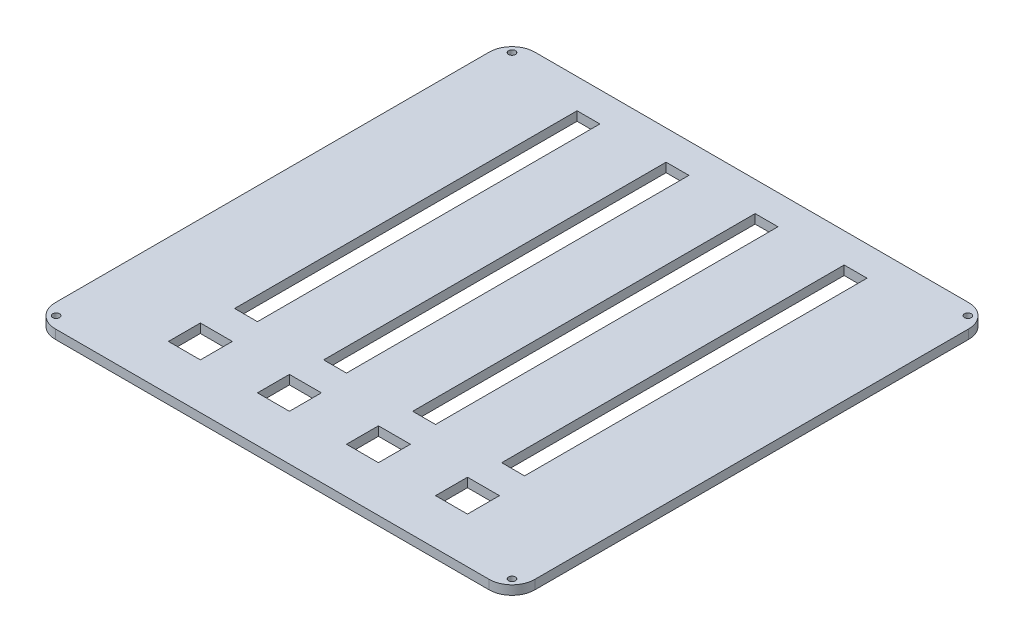
SolidWorks part; units mm, degrees
ref_plane "Front Plane" through (0, 0, 0) normal (0, 0, 1) x (1, 0, 0)
ref_plane "Top Plane" through (0, 0, 0) normal (0, 1, 0) x (1, 0, 0)
ref_plane "Right Plane" through (0, 0, 0) normal (1, 0, 0) x (0, 0, -1)
sketch "Sketch1" plane through (0, 0, 0) normal (0, 1, 0) x (1, 0, 0)
  line L0 (-101, -101) -> (-101, 101)
  line L5 (-105, -105) -> (105, -105)
  line L6 (-105, -105) -> (-105, 105)
  line L7 (-105, 105) -> (105, 105)
  line L8 (105, -105) -> (105, 105)
  line L9 (-101, 101) -> (101, 101)
  line L10 (101, -101) -> (101, 101)
  line L11 (-101, -101) -> (101, -101)
  line L12 (-101, 101) -> (-99.8333, 99.8333) construction
  line L13 (-55, 0) -> (55, 0) construction
  line L14 (-101, -101) -> (-99.8333, -99.8333) construction
  line L15 (0, -55) -> (0, 55) construction
  line L16 (101, -101) -> (99.8333, -99.8333) construction
  line L17 (101, 101) -> (99.8333, 99.8333) construction
  circle A1 centre (-99.8333, 99.8333) radius 1.5
  circle A2 centre (-99.8333, -99.8333) radius 1.5
  circle A3 centre (99.8333, -99.8333) radius 1.5
  circle A4 centre (99.8333, 99.8333) radius 1.5
  point P0 (0, 0)
  point P6 (-105, 0)
  point P7 (0, 105)
  dimension "D3" = 4
  dimension "D4" = 3
  dimension "D1" = 210
  dimension "D2" = 210
  dimension "D5" = 1.65
  dimension "D6" = 45
extrude "MainExtrude" add sketch "Sketch1" along normal blind 4 contours L6 L5 L8 L7
extrude "ScrewHoles" cut sketch "Sketch1<6>" along normal up to surface (4 mm away) contours A1 | A2 | A3 | A4 up to face at (0, 4, 0)
sketch "Sketch1<6>" plane through (0, 0, 0) normal (0, 1, 0) x (1, 0, 0) same geometry as "Sketch1"
fillet "RoundedCorners" radius 10 4 edges at (-105, 2, -105) (-105, 2, 105) (105, 2, -105) (105, 2, 105)
sketch "Sketch2" plane through (0, 0, 0) normal (0, -1, 0) x (1, 0, 0)
  line L0 (-17.92, 37.135) -> (17.92, 37.135) construction
  line L1 (2.2, 0) -> (-2.2, 0) construction
  circle A0 centre (-17.92, 37.135) radius 0.98
  circle A1 centre (-17.92, 37.135) radius 2
  circle A2 centre (17.92, 37.135) radius 2
  circle A3 centre (17.92, 37.135) radius 0.98
  circle A4 centre (-17.92, -37.135) radius 0.98
  circle A5 centre (-17.92, -37.135) radius 2
  circle A6 centre (17.92, -37.135) radius 0.98
  circle A7 centre (17.92, -37.135) radius 2
  point P3 (0, 37.135)
  dimension "D1" = 1.96
  dimension "D2" = 4
  dimension "D4" = 37.135
  dimension "D5" = 35.84
  dimension "D6" = 74.27
  dimension "D3" = 2
extrude "PCBHoles" [suppressed] add sketch "Sketch2" along normal blind 2
fillet "PCBRounds" [suppressed] radius 2
sketch "Sketch3" plane through (0, 4, 0) normal (0, 1, 0) x (1, 0, 0)
  line L0 (-105, -95) -> (-105, 95) construction
  line L1 (-65.5, -85) -> (-51.5, -85)
  line L2 (-65.5, -85) -> (-65.5, -71)
  line L3 (-65.5, -71) -> (-51.5, -71)
  line L4 (-51.5, -85) -> (-51.5, -71)
  line L5 (-65.5, -85) -> (-51.5, -71) construction
  line L6 (-65.5, -71) -> (-51.5, -85) construction
  line L7 (-95, -105) -> (95, -105) construction
  line L8 (-26.5, -85) -> (-26.5, -71)
  line L9 (-26.5, -85) -> (-12.5, -85)
  line L10 (-12.5, -85) -> (-12.5, -71)
  line L11 (-26.5, -71) -> (-12.5, -71)
  line L12 (12.5, -85) -> (12.5, -71)
  line L13 (12.5, -85) -> (26.5, -85)
  line L14 (26.5, -85) -> (26.5, -71)
  line L15 (12.5, -71) -> (26.5, -71)
  line L16 (51.5, -85) -> (51.5, -71)
  line L17 (51.5, -85) -> (65.5, -85)
  line L18 (65.5, -85) -> (65.5, -71)
  line L19 (51.5, -71) -> (65.5, -71)
  line L20 (105, -95) -> (105, 95) construction
  line L21 (-24.5, 92) -> (-24.5, -58)
  line L22 (-63.5, 92) -> (-53.5, 92)
  line L23 (-63.5, 92) -> (-63.5, -58)
  line L24 (-63.5, -58) -> (-53.5, -58)
  line L25 (-53.5, 92) -> (-53.5, -58)
  line L26 (-63.5, 92) -> (-53.5, -58) construction
  line L27 (-63.5, -58) -> (-53.5, 92) construction
  line L28 (-24.5, 92) -> (-14.5, 92)
  line L29 (-14.5, 92) -> (-14.5, -58)
  line L30 (-24.5, -58) -> (-14.5, -58)
  line L31 (-24.5, -58) -> (-14.5, 92) construction
  line L32 (-24.5, 92) -> (-14.5, -58) construction
  line L33 (14.5, 92) -> (14.5, -58)
  line L34 (14.5, 92) -> (24.5, 92)
  line L35 (24.5, 92) -> (24.5, -58)
  line L36 (14.5, -58) -> (24.5, -58)
  line L37 (14.5, -58) -> (24.5, 92) construction
  line L38 (14.5, 92) -> (24.5, -58) construction
  line L39 (53.5, 92) -> (53.5, -58)
  line L40 (53.5, 92) -> (63.5, 92)
  line L41 (63.5, 92) -> (63.5, -58)
  line L42 (53.5, -58) -> (63.5, -58)
  line L43 (53.5, -58) -> (63.5, 92) construction
  line L44 (53.5, 92) -> (63.5, -58) construction
  line L45 (-26.5, -71) -> (-12.5, -85)
  line L46 (12.5, -71) -> (26.5, -85)
  line L47 (51.5, -71) -> (65.5, -85)
  line L49 (-70, 98) -> (70, 98) construction
  line L50 (-70, 98) -> (-70, -62) construction
  line L51 (-70, -62) -> (70, -62) construction
  line L52 (70, 98) -> (70, -62) construction
  line L53 (-70, 98) -> (70, -62) construction
  line L54 (-70, -62) -> (70, 98) construction
  point P0 (-58.5, -78)
  point P23 (-58.5, 17)
  point P29 (-19.5, 17)
  point P35 (19.5, 17)
  point P40 (58.5, 17)
  point P45 (-19.5, -78)
  point P46 (19.5, -78)
  point P47 (58.5, -78)
  dimension "D1" = 14
  dimension "D2" = 39.5
  dimension "D3" = 20
  dimension "D5" = 39.5
  dimension "D6" = 150
  dimension "D7" = 10
  dimension "D8" = 95
  dimension "D9" = 4
  dimension "D10" = 160
  dimension "D11" = 140
  dimension "D12" = 6.5
  dimension "D13" = 4
  dimension "D4" = 4
extrude "Cutouts" cut sketch "Sketch3" against normal blind 10 contours L23 L22 L25 L24 | L21 L30 L29 L28 | L33 L36 L35 L34 | L39 L42 L41 L40 | L2 L1 L4 L3 | L8 L11 L10 L9 | L12 L15 L14 L13 | L16 L19 L18 L17
sketch "Sketch4" plane through (0, 0, 0) normal (0, -1, 0) x (1, 0, 0)
  circle A0 centre (-70, 62) radius 1.25
  circle A1 centre (70, 62) radius 1.25
  circle A2 centre (70, -98) radius 1.25
  circle A3 centre (-70, -98) radius 1.25
  dimension "D1" = 2.5
sketch "Sketch5" plane through (0, 4, 0) normal (0, 1, 0) x (1, 0, 0)
  line L1 (-102.1071, -17.908) -> (-66.2671, -17.908) construction
  line L2 (-102.1071, -17.908) -> (-102.1071, -92.178) construction
  line L3 (-102.1071, -92.178) -> (-66.2671, -92.178) construction
  line L4 (-66.2671, -17.908) -> (-66.2671, -92.178) construction
  circle A0 centre (-102.1071, -17.908) radius 2
  circle A1 centre (-102.1071, -17.908) radius 0.98
  circle A2 centre (-66.2671, -17.908) radius 2
  circle A3 centre (-66.2671, -17.908) radius 0.98
  circle A4 centre (-66.2671, -92.178) radius 2
  circle A5 centre (-66.2671, -92.178) radius 0.98
  circle A6 centre (-102.1071, -92.178) radius 2
  circle A7 centre (-102.1071, -92.178) radius 0.98
  dimension "D3" = 4
  dimension "D4" = 1.96
  dimension "D1" = 35.84
  dimension "D2" = 74.27
extrude "Boss-Extrude1" [suppressed] add sketch "Sketch5" against normal blind 8
fillet "Fillet1" [suppressed] radius 0.5
sketch "Sketch6" plane through (0, 0, 0) normal (0, -1, 0) x (1, 0, 0)
  circle A0 centre (-70, 62) radius 2
  circle A1 centre (-70, 62) radius 0.98
  circle A2 centre (70, 62) radius 2
  circle A3 centre (70, 62) radius 0.98
  circle A4 centre (70, -98) radius 2
  circle A5 centre (70, -98) radius 0.98
  circle A6 centre (-70, -98) radius 2
  circle A7 centre (-70, -98) radius 0.98
  dimension "D1" = 4
  dimension "D2" = 1.96
extrude "Cut-Extrude1" cut sketch "Sketch6" against normal blind 1 contours A7 | A5 | A3 | A1
